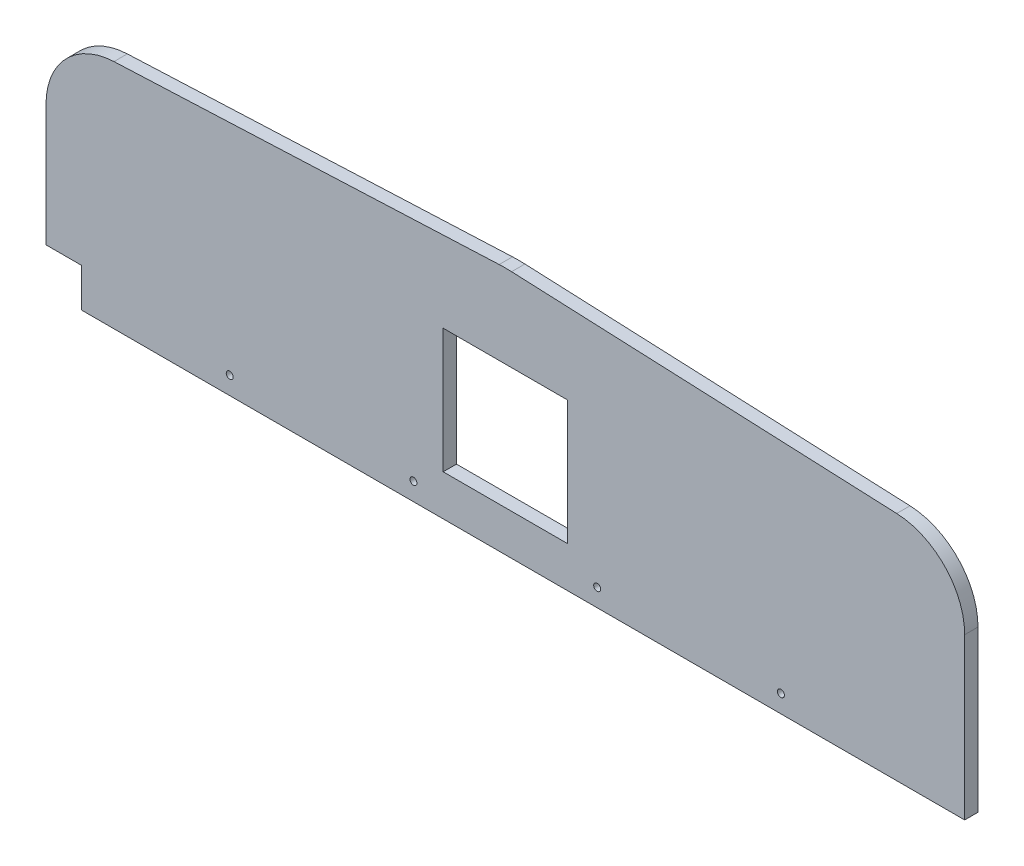
SolidWorks part; units mm, degrees
material "PC High Viscosity"
ref_plane "Front Plane" through (0, 0, 0) normal (0, 0, 1) x (1, 0, 0)
ref_plane "Top Plane" through (0, 0, 0) normal (0, 1, 0) x (1, 0, 0)
ref_plane "Right Plane" through (0, 0, 0) normal (1, 0, 0) x (0, 0, -1)
sketch "Sketch2" plane through (0, 0, 0) normal (0, 0, 1) x (1, 0, 0)
  line L0 (-328.3315, 55.6895) -> (-328.3315, 192.5895)
  line L1 (-328.3315, 192.5895) -> (0, 206.9465)
  line L2 (0, 206.9465) -> (328.2858, 192.5895)
  line L3 (328.2858, 192.5895) -> (328.2858, 55.6895)
  line L4 (328.2858, 55.6895) -> (328.2858, 29.2895)
  line L6 (328.2858, 29.2895) -> (-328.3315, 29.2895)
  line L7 (-328.3315, 29.2895) -> (-328.3315, 55.6895)
  dimension "D1" = 151.257
  dimension "D7" = 328.2858
  dimension "D8" = 136.9
  dimension "D9" = 26.4
extrude "Boss-Extrude1" add sketch "Sketch2" along normal mid plane 9.525
fillet "Fillet1" radius 50.8 2 edges at (328.2858, 192.5895, 0) (-328.3315, 192.5895, 0)
fillet "Fillet2" radius 101.6 1 edges at (0, 206.9465, 0)
sketch "Sketch3" plane through (0, 0, 4.7625) normal (0, 0, 1) x (1, 0, 0)
  line L0 (0, 0) -> (0, 192.0016) construction
  line L1 (-328.3315, 29.2895) -> (-302.9315, 29.2895)
  line L2 (-328.3315, 29.2895) -> (-328.3315, 56.9755)
  line L3 (-328.3315, 56.9755) -> (-302.9315, 56.9755)
  line L4 (-302.9315, 29.2895) -> (-302.9315, 56.9755)
  line L5 (0, 192.0016) -> (0, -60.0751) construction
  dimension "D1" = 25.4
  dimension "D2" = 27.686
extrude "Cut-Extrude1" cut sketch "Sketch3" against normal through all
sketch "Sketch5" plane through (0, 0, 4.7625) normal (0, 0, 1) x (1, 0, 0)
  line L1 (-44.45, 147.336) -> (44.45, 147.336)
  line L2 (-44.45, 147.336) -> (-44.45, 58.436)
  line L3 (-44.45, 58.436) -> (44.45, 58.436)
  line L4 (44.45, 147.336) -> (44.45, 58.436)
  line L5 (-44.45, 147.336) -> (44.45, 58.436) construction
  line L6 (-44.45, 58.436) -> (44.45, 147.336) construction
  point P0 (0, 102.886)
  dimension "D1" = 88.9
  dimension "D2" = 88.9
extrude "Cut-Extrude2" cut sketch "Sketch5" against normal through all
hole_wizard "Tap Drill for M6x1.0 Tap1" positions "Sketch7" profile "Sketch6" hole size "M6x1.0" standard "ANSI Metric" end condition through all
sketch "Sketch7" plane through (0, 0, 4.7625) normal (0, 0, 1) x (1, 0, 0)
  line L0 (-302.9315, 29.2895) -> (328.2858, 29.2895) construction
  line L1 (-328.3315, 143.9623) -> (-328.3315, 56.9755) construction
  point P0 (-197.0135, 41.9895)
  point P2 (-65.6955, 41.9895)
  point P4 (65.6225, 41.9895)
  point P6 (196.9405, 41.9895)
  dimension "D1" = 12.7
  dimension "D2" = 131.318
  dimension "D3" = 131.318
  dimension "D4" = 131.318
  dimension "D5" = 131.318
sketch "Sketch6" plane through (-197.0135, 41.9895, 4.7625) normal (1, 0, 0) x (0, -1, 0)
  line L0 (0, 0) -> (0, 9.525)
  line L1 (0, 9.525) -> (2.5, 9.525)
  line L2 (2.5, 9.525) -> (2.5, 0)
  line L5 (2.5, 0) -> (0, 0)
  line L11 (0, -6.35) -> (0, 107.95) construction
  dimension "Thru Hole Dia." = 5
  dimension "Thru Hole Depth" = 9.525
